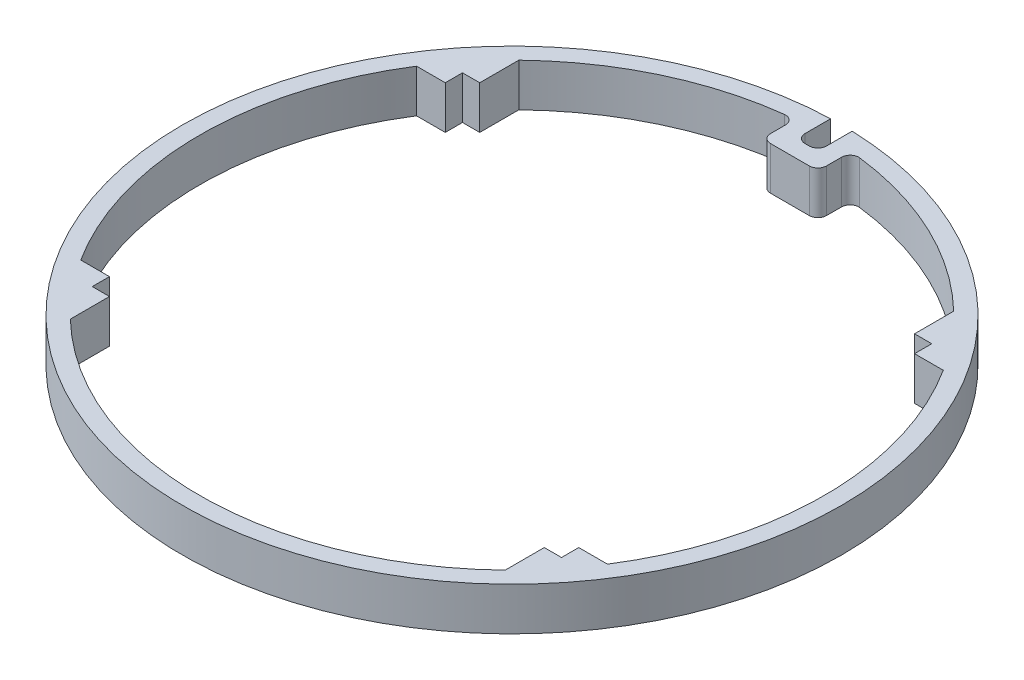
SolidWorks part; units mm, degrees
ref_plane "Front Plane" through (0, 0, 0) normal (0, 0, 1) x (1, 0, 0)
ref_plane "Top Plane" through (0, 0, 0) normal (0, 1, 0) x (1, 0, 0)
ref_plane "Right Plane" through (0, 0, 0) normal (1, 0, 0) x (0, 0, -1)
sketch "Sketch1" plane through (0, 0, 0) normal (0, 1, 0) x (1, 0, 0)
  line L4 (-0.5, 68.5483) -> (0.5, 68.5483)
  line L13 (-4.4989, 64.5455) -> (4.5046, 64.5455)
  line L25 (50.5, 52.0889) -> (50.5, 43)
  line L27 (54.5, 39) -> (61.176, 39)
  line L29 (50.5, -52.0889) -> (50.5, -43)
  line L31 (54.5, -39) -> (61.176, -39)
  line L33 (-54.5, -39) -> (-61.176, -39)
  line L35 (-50.5, -43) -> (-50.5, -52.0889)
  line L36 (-6.4989, 70.0362) -> (-6.4989, 66.5455)
  line L37 (-2.5, 76.5092) -> (-2.5, 70.5483)
  line L38 (6.5046, 66.5455) -> (6.5046, 70.0355)
  line L39 (-54.5, 39) -> (-54.5, 43)
  line L42 (-54.5, 43) -> (-50.5, 43)
  line L43 (-50.5, 52.0889) -> (-50.5, 43)
  line L44 (-54.5, 39) -> (-61.176, 39)
  line L45 (-54.5, -39) -> (-54.5, -43)
  line L46 (-54.5, -43) -> (-50.5, -43)
  line L47 (54.5, -39) -> (54.5, -43)
  line L48 (54.5, -43) -> (50.5, -43)
  line L49 (50.5, 43) -> (54.5, 43)
  line L50 (54.5, 43) -> (54.5, 39)
  line L51 (2.5, 76.5092) -> (2.5, 70.5483)
  arc A0 (-2.5, 76.5092) -> (2.5, 76.5092) centre (0, 0) ccw
  arc A1 (-8.7398, 72.0216) -> (-50.5, 52.0889) centre (0, 0) ccw
  arc A2 (6.5046, 70.0355) -> (8.7457, 72.0209) centre (8.5046, 70.0355) cw
  arc A3 (-6.4989, 70.0362) -> (-8.7398, 72.0216) centre (-8.4989, 70.0362) ccw
  arc A4 (-2.5, 70.5483) -> (-0.5, 68.5483) centre (-0.5, 70.5483) ccw
  arc A5 (0.5, 68.5483) -> (2.5, 70.5483) centre (0.5, 70.5483) ccw
  arc A6 (4.5046, 64.5455) -> (6.5046, 66.5455) centre (4.5046, 66.5455) ccw
  arc A7 (-6.4989, 66.5455) -> (-4.4989, 64.5455) centre (-4.4989, 66.5455) ccw
  arc A9 (-50.5, -52.0889) -> (50.5, -52.0889) centre (0, 0) ccw
  arc A10 (61.176, -39) -> (61.176, 39) centre (0, 0) ccw
  arc A11 (50.5, 52.0889) -> (8.7457, 72.0209) centre (0, 0) ccw
  arc A12 (-61.176, 39) -> (-61.176, -39) centre (0.3145, 0) ccw
  dimension "D1" = 2
  dimension "D5" = 76.55
extrude "Boss-Extrude1" add sketch "Sketch1" along normal blind 10
